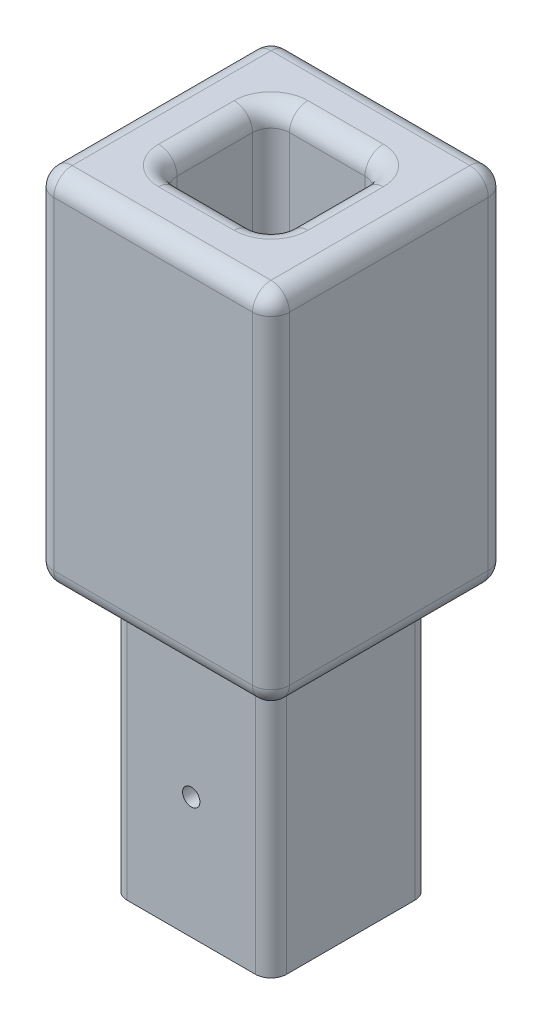
SolidWorks part; units mm, degrees
ref_plane "Front Plane" through (0, 0, 0) normal (0, 0, 1) x (1, 0, 0)
ref_plane "Top Plane" through (0, 0, 0) normal (0, 1, 0) x (1, 0, 0)
ref_plane "Right Plane" through (0, 0, 0) normal (1, 0, 0) x (0, 0, -1)
sketch "Sketch1" plane through (0, 0, 0) normal (0, 1, 0) x (1, 0, 0)
  line L0 (-9.0805, -9.0805) -> (-9.0805, 9.0805)
  line L1 (12.8905, -12.8905) -> (-12.8905, -12.8905)
  line L2 (12.8905, -12.8905) -> (12.8905, 12.8905)
  line L3 (12.8905, 12.8905) -> (-12.8905, 12.8905)
  line L4 (-12.8905, -12.8905) -> (-12.8905, 12.8905)
  line L5 (12.8905, -12.8905) -> (-12.8905, 12.8905) construction
  line L6 (12.8905, 12.8905) -> (-12.8905, -12.8905) construction
  line L7 (9.0805, 9.0805) -> (-9.0805, 9.0805)
  line L8 (9.0805, -9.0805) -> (9.0805, 9.0805)
  line L9 (9.0805, -9.0805) -> (-9.0805, -9.0805)
  line L11 (19.05, -19.05) -> (-19.05, -19.05)
  line L12 (19.05, -19.05) -> (19.05, 19.05)
  line L13 (19.05, 19.05) -> (-19.05, 19.05)
  line L14 (-19.05, -19.05) -> (-19.05, 19.05)
  line L15 (19.05, -19.05) -> (-19.05, 19.05) construction
  line L16 (19.05, 19.05) -> (-19.05, -19.05) construction
  point P0 (0, 0)
  point P10 (0, 0)
  dimension "D1" = 25.781
  dimension "D3" = 38.1
  dimension "D4" = 38.1
  dimension "D2" = 3.81
extrude "Boss-Extrude1" add sketch "Sketch1" along normal blind 101.6 contours L4 L1 L2 L3 L8 L9 L0 L7 region at (0, 0, 12.5259)
extrude "Boss-Extrude2" add sketch "Sketch1<3>" along normal up to surface (101.6 mm away) from offset 43.4 contours L14 L11 L12 L13 L1 L4 L3 L2 region at (0, 0, 18.5112) up to face at (0, 101.6, 0)
sketch "Sketch1<3>" plane through (0, 0, 0) normal (0, 1, 0) x (1, 0, 0) same geometry as "Sketch1"
fillet "Fillet1" radius 2.54 4 edges at (12.8905, 21.7, -12.8905) (12.8905, 21.7, 12.8905) (-12.8905, 21.7, 12.8905) (-12.8905, 21.7, -12.8905)
fillet "Fillet2" radius 2.9845 24 edges at (-9.0805, 101.6, 0) (-9.0805, 0, 0) (-9.0805, 50.8, -9.0805) (0, 101.6, -9.0805) (0, 0, -9.0805) (0, 101.6, 9.0805) (-9.0805, 50.8, 9.0805) (0, 0, 9.0805) (9.0805, 50.8, -9.0805) (9.0805, 101.6, 0) (9.0805, 50.8, 9.0805) (9.0805, 0, 0) (19.05, 72.5, -19.05) (19.05, 43.4, 0) (19.05, 101.6, 0) (0, 43.4, 19.05) (0, 101.6, 19.05) (19.05, 72.5, 19.05) (-19.05, 43.4, 0) (-19.05, 72.5, -19.05) (-19.05, 101.6, 0) (-19.05, 72.5, 19.05) (0, 43.4, -19.05) (0, 101.6, -19.05)
sketch "Sketch2" plane through (0, 0, -12.8905) normal (0, 0, -1) x (-1, 0, 0)
  line L0 (0, 43.4) -> (0, 19.6431)
  line L1 (-10.3505, 43.4) -> (10.3505, 43.4) construction
  circle A0 centre (0, 19.6431) radius 1.4
extrude "Cut-Extrude1" cut sketch "Sketch2" against normal blind 37.592 contours A0 region at (0.9619, 18.6811, -12.8905)
